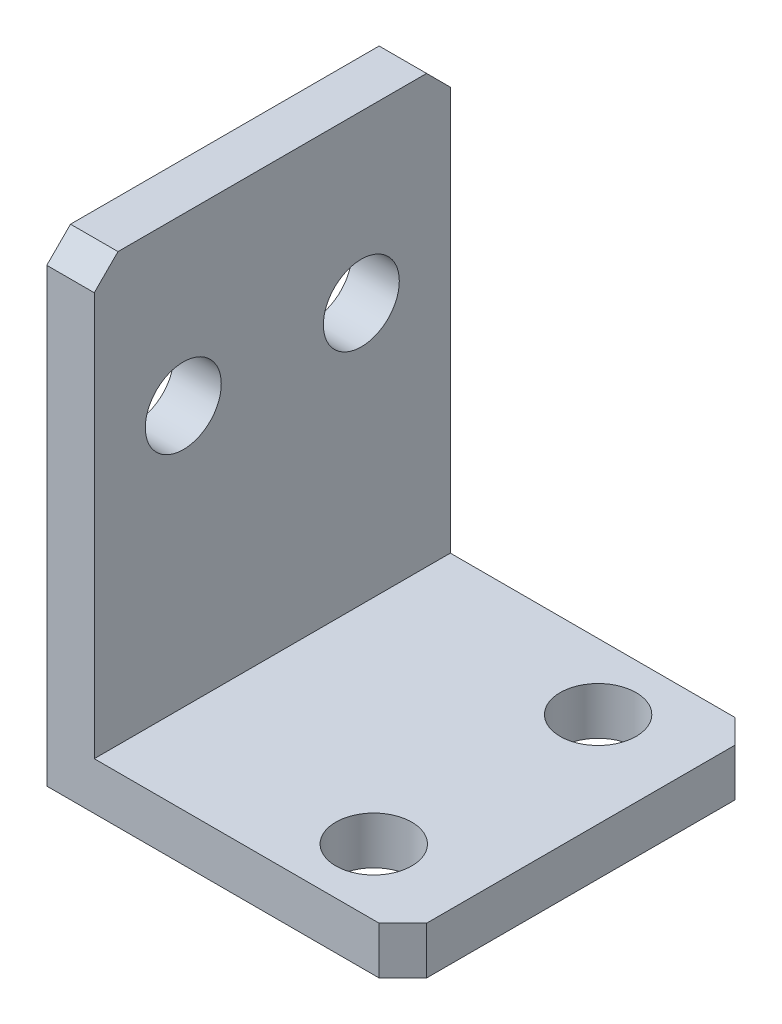
SolidWorks part; units mm, degrees
material "6060 Alloy"
ref_plane "Front Plane" through (0, 0, 0) normal (0, 0, 1) x (1, 0, 0)
ref_plane "Top Plane" through (0, 0, 0) normal (0, 1, 0) x (1, 0, 0)
ref_plane "Right Plane" through (0, 0, 0) normal (1, 0, 0) x (0, 0, -1)
sketch "Sketch1" plane through (0, 0, 0) normal (0, 0, 1) x (1, 0, 0)
  line L0 (0, 0) -> (0, 20)
  line L1 (0, 20) -> (2, 20)
  line L2 (2, 20) -> (2, 2)
  line L3 (2, 2) -> (15, 2)
  line L4 (15, 2) -> (15, 0)
  line L5 (15, 0) -> (0, 0)
  dimension "D1" = 15
  dimension "D2" = 20
  dimension "D3" = 2
extrude "Body" add sketch "Sketch1" along normal blind 15
chamfer "Chamfer1" distance 1 angle 45 4 edges at (15, 1, 0) (15, 1, 15) (1, 20, 0) (1, 20, 15)
hole_wizard "Ø3.2 (3.2) ForSensor" positions "Sketch4" profile "Sketch5" hole size "Ø3.2" standard "ANSI Metric" end condition through all
sketch "Sketch4" plane through (0, 2, 0) normal (0, 1, 0) x (1, 0, 0)
  line L0 (15, -7.5) -> (10.0418, -7.5) construction
  line L1 (15, -14) -> (15, -1) construction
  line L3 (0, -14) -> (0, -1) construction
  point P0 (11, -2.775)
  point P2 (11, -12.225)
  dimension "D1" = 9.45
  dimension "D2" = 11
sketch "Sketch5" plane through (11, 2, 2.775) normal (1, 0, 0) x (0, 0, 1)
  line L0 (0, 0) -> (0, 2)
  line L1 (0, 2) -> (1.6, 2)
  line L2 (1.6, 2) -> (1.6, 0)
  line L5 (1.6, 0) -> (0, 0)
  line L11 (0, -6.35) -> (0, 107.95) construction
  dimension "Thru Hole Dia." = 3.2
  dimension "Thru Hole Depth" = 2
hole_wizard "Ø3.2 (3.2) ForCarriage" positions "Sketch6" profile "Sketch7" hole size "Ø3.2" standard "ANSI Metric" end condition through all
sketch "Sketch6" plane through (2, 0, 0) normal (1, 0, 0) x (0, 0, -1)
  line L0 (-7.5, 20) -> (-7.5, 16.9192) construction
  line L1 (-14, 20) -> (-1, 20) construction
  line L3 (-14, 0) -> (-1, 0) construction
  point P0 (-11.25, 13)
  point P2 (-3.75, 13)
  dimension "D1" = 7.5
  dimension "D2" = 13
sketch "Sketch7" plane through (2, 13, 11.25) normal (0, 1, 0) x (0, 0, -1)
  line L0 (0, 0) -> (0, 2)
  line L1 (0, 2) -> (1.6, 2)
  line L2 (1.6, 2) -> (1.6, 0)
  line L5 (1.6, 0) -> (0, 0)
  line L11 (0, -6.35) -> (0, 107.95) construction
  dimension "Thru Hole Dia." = 3.2
  dimension "Thru Hole Depth" = 2
